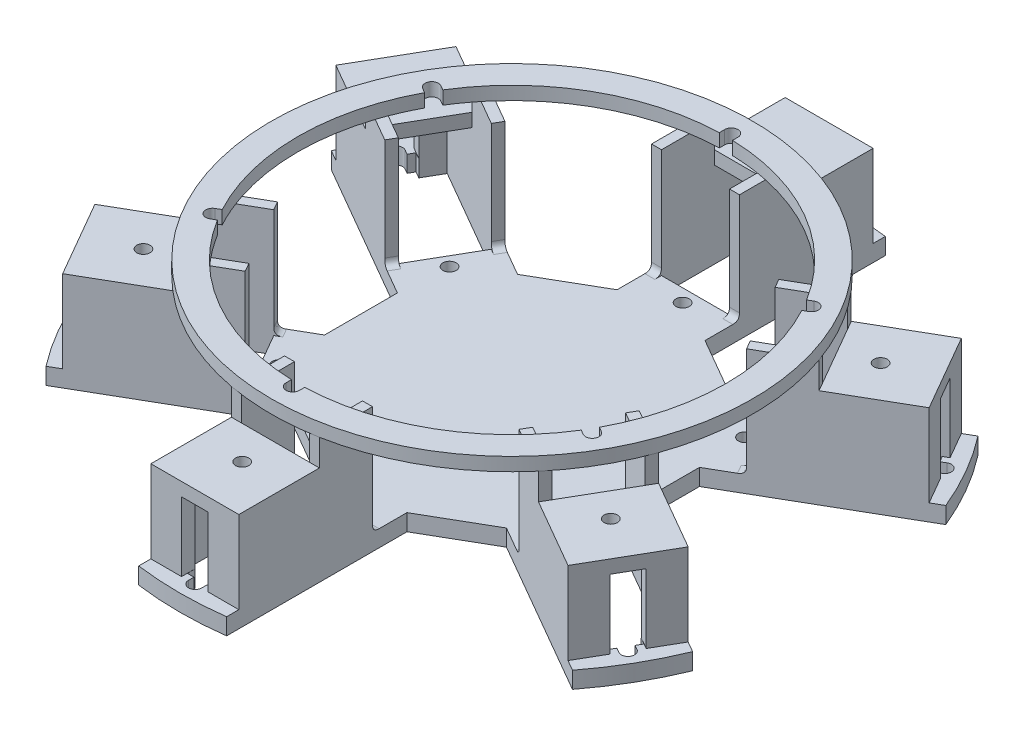
SolidWorks part; units mm, degrees
material "ABS"
ref_plane "Front" through (0, 0, 0) normal (0, 0, 1) x (1, 0, 0)
ref_plane "Top" through (0, 0, 0) normal (0, 1, 0) x (1, 0, 0)
ref_plane "Right" through (0, 0, 0) normal (1, 0, 0) x (0, 0, -1)
sketch "Sketch1" plane through (0, 0, 0) normal (0, 1, 0) x (1, 0, 0)
  line L0 (0, -63.5) -> (0, -61.8094) construction
  line L1 (0, 63.5) -> (-54.9926, 31.75) construction
  line L2 (-54.9926, 31.75) -> (-54.9926, -31.75) construction
  line L3 (-54.9926, -31.75) -> (0, -63.5) construction
  line L4 (0, -63.5) -> (54.9926, -31.75) construction
  line L5 (54.9926, -31.75) -> (54.9926, 31.75) construction
  line L6 (54.9926, 31.75) -> (0, 63.5) construction
  line L7 (47.0396, 34.6639) -> (27.121, 23.1639)
  line L8 (-6.5, 58.0694) -> (-2.5207, 58.0694)
  line L9 (-6.5, 58.0694) -> (-6.5, 35.0694)
  line L10 (-6.5, 35.0694) -> (6.5, 35.0694)
  line L11 (6.5, 58.0694) -> (6.5, 35.0694)
  line L12 (-6.5, 58.0694) -> (6.5, 35.0694) construction
  line L13 (-6.5, 35.0694) -> (6.5, 58.0694) construction
  line L14 (47.0396, 34.6639) -> (49.0292, 31.2177)
  line L15 (53.5396, 23.4055) -> (33.621, 11.9055)
  line L16 (27.121, 23.1639) -> (33.621, 11.9055)
  line L17 (53.5396, -23.4055) -> (33.621, -11.9055)
  line L18 (53.5396, -23.4055) -> (51.5499, -26.8517)
  line L19 (47.0396, -34.6639) -> (27.121, -23.1639)
  line L20 (33.621, -11.9055) -> (27.121, -23.1639)
  line L21 (6.5, -58.0694) -> (6.5, -35.0694)
  line L22 (6.5, -58.0694) -> (2.5207, -58.0694)
  line L23 (-6.5, -58.0694) -> (-6.5, -35.0694)
  line L24 (6.5, -35.0694) -> (-6.5, -35.0694)
  line L25 (-47.0396, -34.6639) -> (-27.121, -23.1639)
  line L26 (-47.0396, -34.6639) -> (-49.0292, -31.2177)
  line L27 (-53.5396, -23.4055) -> (-33.621, -11.9055)
  line L28 (-27.121, -23.1639) -> (-33.621, -11.9055)
  line L29 (-53.5396, 23.4055) -> (-33.621, 11.9055)
  line L30 (-53.5396, 23.4055) -> (-51.5499, 26.8517)
  line L31 (-47.0396, 34.6639) -> (-27.121, 23.1639)
  line L32 (-33.621, 11.9055) -> (-27.121, 23.1639)
  line L33 (-1.27, 60.5394) -> (-1.27, 59.5132)
  line L34 (-1.27, 59.5132) -> (-2.5207, 59.5132)
  line L35 (-2.5207, 59.5132) -> (-2.5207, 58.0694)
  line L37 (2.5207, 59.5132) -> (2.5207, 58.0694)
  line L38 (1.27, 59.5132) -> (2.5207, 59.5132)
  line L39 (1.27, 60.5394) -> (1.27, 59.5132)
  line L40 (0, 53.87) -> (0, 63.5) construction
  line L41 (51.7937, 31.3696) -> (50.9049, 30.8564)
  line L42 (50.9049, 30.8564) -> (50.2796, 31.9396)
  line L43 (50.2796, 31.9396) -> (49.0292, 31.2177)
  line L45 (52.8003, 27.5736) -> (51.5499, 26.8517)
  line L46 (52.1749, 28.6567) -> (52.8003, 27.5736)
  line L47 (53.0637, 29.1699) -> (52.1749, 28.6567)
  line L48 (53.0637, -29.1699) -> (52.1749, -28.6567)
  line L49 (52.1749, -28.6567) -> (52.8003, -27.5736)
  line L50 (52.8003, -27.5736) -> (51.5499, -26.8517)
  line L52 (50.2796, -31.9396) -> (49.0292, -31.2177)
  line L53 (50.9049, -30.8564) -> (50.2796, -31.9396)
  line L54 (51.7937, -31.3696) -> (50.9049, -30.8564)
  line L55 (1.27, -60.5394) -> (1.27, -59.5132)
  line L56 (1.27, -59.5132) -> (2.5207, -59.5132)
  line L57 (2.5207, -59.5132) -> (2.5207, -58.0694)
  line L59 (-2.5207, -59.5132) -> (-2.5207, -58.0694)
  line L60 (-1.27, -59.5132) -> (-2.5207, -59.5132)
  line L61 (-1.27, -60.5394) -> (-1.27, -59.5132)
  line L62 (-51.7937, -31.3696) -> (-50.9049, -30.8564)
  line L63 (-50.9049, -30.8564) -> (-50.2796, -31.9396)
  line L64 (-50.2796, -31.9396) -> (-49.0292, -31.2177)
  line L66 (-52.8003, -27.5736) -> (-51.5499, -26.8517)
  line L67 (-52.1749, -28.6567) -> (-52.8003, -27.5736)
  line L68 (-53.0637, -29.1699) -> (-52.1749, -28.6567)
  line L69 (-53.0637, 29.1699) -> (-52.1749, 28.6567)
  line L70 (-52.1749, 28.6567) -> (-52.8003, 27.5736)
  line L71 (-52.8003, 27.5736) -> (-51.5499, 26.8517)
  line L73 (-50.2796, 31.9396) -> (-49.0292, 31.2177)
  line L74 (-50.9049, 30.8564) -> (-50.2796, 31.9396)
  line L75 (-51.7937, 31.3696) -> (-50.9049, 30.8564)
  line L76 (2.5207, 58.0694) -> (6.5, 58.0694)
  line L77 (-49.0292, 31.2177) -> (-47.0396, 34.6639)
  line L78 (-51.5499, -26.8517) -> (-53.5396, -23.4055)
  line L79 (0, -58.0694) -> (0, 54.9926) construction
  line L80 (-2.5207, -58.0694) -> (-6.5, -58.0694)
  line L81 (49.0292, -31.2177) -> (47.0396, -34.6639)
  line L82 (51.5499, 26.8517) -> (53.5396, 23.4055)
  circle A0 centre (0, 0) radius 63.5
  circle A1 centre (0, 0) radius 54.9926 construction
  arc A2 (1.27, 60.5394) -> (-1.27, 60.5394) centre (0, 60.5394) ccw
  circle A3 centre (0, 32.5994) radius 1.27
  circle A5 centre (28.2319, 16.2997) radius 1.27
  circle A7 centre (28.2319, -16.2997) radius 1.27
  circle A9 centre (0, -32.5994) radius 1.27
  circle A11 centre (-28.2319, -16.2997) radius 1.27
  circle A13 centre (-28.2319, 16.2997) radius 1.27
  circle A14 centre (-52.4287, 30.2697) radius 1.27 [skipped]
  circle A15 centre (-52.4287, -30.2697) radius 1.27 [skipped]
  circle A16 centre (0, -60.5394) radius 1.27 [skipped]
  circle A17 centre (52.4287, -30.2697) radius 1.27 [skipped]
  circle A18 centre (52.4287, 30.2697) radius 1.27 [skipped]
  arc A19 (53.0637, 29.1699) -> (51.7937, 31.3696) centre (52.4287, 30.2697) ccw
  arc A20 (51.7937, -31.3696) -> (53.0637, -29.1699) centre (52.4287, -30.2697) ccw
  arc A21 (-1.27, -60.5394) -> (1.27, -60.5394) centre (0, -60.5394) ccw
  arc A22 (-53.0637, -29.1699) -> (-51.7937, -31.3696) centre (-52.4287, -30.2697) ccw
  arc A23 (-51.7937, 31.3696) -> (-53.0637, 29.1699) centre (-52.4287, 30.2697) ccw
  point P3 (0, 46.5694)
  point P11 (0, 0)
  point P13 (0, 0)
  point P14 (0, 0)
  point P64 (0, 0)
  point P69 (0, 52.67)
  point P120 (0, 0)
  point P121 (0, 0)
  point P122 (0, 46.5694)
  dimension "D1" = 127
  dimension "D4" = 2.54
  dimension "D5" = 2.54
  dimension "D2" = 23
  dimension "D3" = 13
  dimension "D6" = 27.94
  dimension "D7" = 13.97
  dimension "D9" = 6
  dimension "D10" = 1.4438
  dimension "D8" = 6
extrude "Boss-Extrude2" add sketch "Sketch1" along normal blind 3.175
sketch "Sketch2" plane through (0, 3.175, 0) normal (0, 1, 0) x (1, 0, 0)
  line L0 (0, 0) -> (-8.405, 62.9413) construction
  line L1 (0, 0) -> (-50.3063, 38.7496) construction
  line L2 (0, 0) -> (-25.4, 43.9941) construction
  line L3 (-50.3063, 38.7496) -> (-8.405, 62.9413) construction
  line L4 (-27.121, 23.1639) -> (-6.5, 35.0694) construction
  line L6 (-8.405, 28.4804) -> (-20.4623, 21.5192)
  line L7 (-20.4623, 21.5192) -> (-50.3063, 38.7496)
  line L8 (-27.121, 23.1639) -> (-47.0396, 34.6639) construction
  line L9 (-8.405, 28.4804) -> (-8.405, 62.9413)
  line L25 (-6.5, 58.0694) -> (-6.5, 35.0694) construction
  line L26 (8.405, 28.4804) -> (8.405, 62.9413)
  line L27 (20.4623, 21.5192) -> (8.405, 28.4804)
  line L28 (20.4623, 21.5192) -> (50.3063, 38.7496)
  line L29 (28.8673, 6.9613) -> (58.7113, 24.1917)
  line L30 (28.8673, -6.9613) -> (28.8673, 6.9613)
  line L31 (28.8673, -6.9613) -> (58.7113, -24.1917)
  line L32 (20.4623, -21.5192) -> (50.3063, -38.7496)
  line L33 (8.405, -28.4804) -> (20.4623, -21.5192)
  line L34 (8.405, -28.4804) -> (8.405, -62.9413)
  line L35 (-8.405, -28.4804) -> (-8.405, -62.9413)
  line L36 (-20.4623, -21.5192) -> (-8.405, -28.4804)
  line L37 (-20.4623, -21.5192) -> (-50.3063, -38.7496)
  line L38 (-28.8673, -6.9613) -> (-58.7113, -24.1917)
  line L39 (-28.8673, 6.9613) -> (-28.8673, -6.9613)
  line L40 (-28.8673, 6.9613) -> (-58.7113, 24.1917)
  circle A0 centre (0, 0) radius 63.5 construction
  arc A1 (-8.405, 62.9413) -> (-50.3063, 38.7496) centre (0, 0) ccw
  arc A7 (50.3063, 38.7496) -> (8.405, 62.9413) centre (0, 0) ccw
  arc A8 (58.7113, -24.1917) -> (58.7113, 24.1917) centre (0, 0) ccw
  arc A9 (8.405, -62.9413) -> (50.3063, -38.7496) centre (0, 0) ccw
  arc A10 (-50.3063, -38.7496) -> (-8.405, -62.9413) centre (0, 0) ccw
  arc A11 (-58.7113, 24.1917) -> (-58.7113, -24.1917) centre (0, 0) ccw
  point P38 (0, 0)
  point P41 (0, 0)
  dimension "D1" = 1.905
  dimension "D2" = 6
extrude "Cut-Extrude1" cut sketch "Sketch2" against normal up to next
sketch "Sketch3" plane through (0, 3.175, 0) normal (0, 1, 0) x (1, 0, 0)
  line L0 (-6.5, 35.0694) -> (6.5, 35.0694) construction
  line L5 (47.0396, 34.6639) -> (27.121, 23.1639)
  line L6 (27.121, 23.1639) -> (26.1685, 24.8137)
  line L8 (-6.5, 58.0694) -> (-6.5, 35.0694)
  line L9 (-6.5, 35.0694) -> (-8.405, 35.0694)
  line L10 (-8.405, 58.7044) -> (-8.405, 35.0694)
  line L11 (0, 60.5394) -> (0, 32.9218) construction
  line L12 (6.5, 35.0694) -> (8.405, 35.0694)
  line L13 (8.405, 58.7044) -> (8.405, 35.0694)
  line L15 (6.5, 58.0694) -> (6.5, 35.0694)
  line L57 (-8.405, 28.4804) -> (-8.405, 62.9413) construction
  line L58 (8.405, 62.9413) -> (8.405, 28.4804) construction
  line L59 (-6.5, 58.0694) -> (6.5, 58.0694)
  line L60 (-8.405, 58.7044) -> (-8.405, 60.6094)
  line L61 (-8.405, 60.6094) -> (8.405, 60.6094)
  line L62 (8.405, 58.7044) -> (8.405, 60.6094)
  line L63 (46.637, 36.6312) -> (26.1685, 24.8137)
  line L64 (33.621, 11.9055) -> (34.5735, 10.2558)
  line L65 (55.042, 22.0733) -> (34.5735, 10.2558)
  line L66 (53.5396, 23.4055) -> (33.621, 11.9055)
  line L67 (47.0396, 34.6639) -> (53.5396, 23.4055)
  line L68 (46.637, 36.6312) -> (48.2868, 37.5837)
  line L69 (48.2868, 37.5837) -> (56.6918, 23.0258)
  line L70 (55.042, 22.0733) -> (56.6918, 23.0258)
  line L71 (52.4287, 30.2697) -> (28.5111, 16.4609) construction
  line L72 (53.5396, -23.4055) -> (33.621, -11.9055)
  line L73 (33.621, -11.9055) -> (34.5735, -10.2558)
  line L74 (55.042, -22.0733) -> (34.5735, -10.2558)
  line L75 (27.121, -23.1639) -> (26.1685, -24.8137)
  line L76 (46.637, -36.6312) -> (26.1685, -24.8137)
  line L77 (47.0396, -34.6639) -> (27.121, -23.1639)
  line L78 (53.5396, -23.4055) -> (47.0396, -34.6639)
  line L79 (55.042, -22.0733) -> (56.6918, -23.0258)
  line L80 (56.6918, -23.0258) -> (48.2868, -37.5837)
  line L81 (46.637, -36.6312) -> (48.2868, -37.5837)
  line L82 (52.4287, -30.2697) -> (28.5111, -16.4609) construction
  line L83 (6.5, -58.0694) -> (6.5, -35.0694)
  line L84 (6.5, -35.0694) -> (8.405, -35.0694)
  line L85 (8.405, -58.7044) -> (8.405, -35.0694)
  line L86 (-6.5, -35.0694) -> (-8.405, -35.0694)
  line L87 (-8.405, -58.7044) -> (-8.405, -35.0694)
  line L88 (-6.5, -58.0694) -> (-6.5, -35.0694)
  line L89 (6.5, -58.0694) -> (-6.5, -58.0694)
  line L90 (8.405, -58.7044) -> (8.405, -60.6094)
  line L91 (8.405, -60.6094) -> (-8.405, -60.6094)
  line L92 (-8.405, -58.7044) -> (-8.405, -60.6094)
  line L93 (0, -60.5394) -> (0, -32.9218) construction
  line L94 (-47.0396, -34.6639) -> (-27.121, -23.1639)
  line L95 (-27.121, -23.1639) -> (-26.1685, -24.8137)
  line L96 (-46.637, -36.6312) -> (-26.1685, -24.8137)
  line L97 (-33.621, -11.9055) -> (-34.5735, -10.2558)
  line L98 (-55.042, -22.0733) -> (-34.5735, -10.2558)
  line L99 (-53.5396, -23.4055) -> (-33.621, -11.9055)
  line L100 (-47.0396, -34.6639) -> (-53.5396, -23.4055)
  line L101 (-46.637, -36.6312) -> (-48.2868, -37.5837)
  line L102 (-48.2868, -37.5837) -> (-56.6918, -23.0258)
  line L103 (-55.042, -22.0733) -> (-56.6918, -23.0258)
  line L104 (-52.4287, -30.2697) -> (-28.5111, -16.4609) construction
  line L105 (-53.5396, 23.4055) -> (-33.621, 11.9055)
  line L106 (-33.621, 11.9055) -> (-34.5735, 10.2558)
  line L107 (-55.042, 22.0733) -> (-34.5735, 10.2558)
  line L108 (-27.121, 23.1639) -> (-26.1685, 24.8137)
  line L109 (-46.637, 36.6312) -> (-26.1685, 24.8137)
  line L110 (-47.0396, 34.6639) -> (-27.121, 23.1639)
  line L111 (-53.5396, 23.4055) -> (-47.0396, 34.6639)
  line L112 (-55.042, 22.0733) -> (-56.6918, 23.0258)
  line L113 (-56.6918, 23.0258) -> (-48.2868, 37.5837)
  line L114 (-46.637, 36.6312) -> (-48.2868, 37.5837)
  line L115 (-52.4287, 30.2697) -> (-28.5111, 16.4609) construction
  point P0 (0, 0)
  point P1 (0, 0)
  point P64 (0, 0)
  point P85 (0, 0)
  dimension "D1" = 6
  dimension "D2" = 1.905
  dimension "D3" = 2.54
extrude "Boss-Extrude3" add sketch "Sketch3" along normal blind 13.208
sketch "Sketch4" plane through (0, 0, -60.6094) normal (0, 0, -1) x (-1, 0, 0)
  line L0 (0, 3.175) -> (0, 16.383) construction
  line L1 (8.405, 3.175) -> (-8.405, 3.175) construction
  line L2 (-8.405, 16.383) -> (8.405, 16.383) construction
  line L4 (-2.54, 16.383) -> (2.54, 16.383)
  line L5 (-2.54, 16.383) -> (-2.54, 3.175)
  line L6 (-2.54, 3.175) -> (2.54, 3.175)
  line L7 (2.54, 16.383) -> (2.54, 3.175)
  line L8 (-2.54, 16.383) -> (2.54, 3.175) construction
  line L9 (-2.54, 3.175) -> (2.54, 16.383) construction
  point P6 (0, 9.779)
  dimension "D1" = 5.08
extrude "Cut-Extrude2" cut sketch "Sketch4" against normal blind 13.208
ref_point "Point1"
pattern_circular "CirPattern2" count 6 every 60 about axis through (0, 3.175, 0) along (0, 1, 0) of "Cut-Extrude2"
fillet "Fillet1" radius 1.27 12 edges at (26.6448, 3.175, -23.9888) (34.0973, 3.175, -11.0807) (34.0973, 3.175, 11.0807) (26.6448, 3.175, 23.9888) (7.4525, 3.175, 35.0694) (-7.4525, 3.175, 35.0694) (-26.6448, 3.175, 23.9888) (-34.0973, 3.175, 11.0807) (-34.0973, 3.175, -11.0807) (-26.6448, 3.175, -23.9888) (-7.4525, 3.175, -35.0694) (7.4525, 3.175, -35.0694) conic rho 0.5
sketch "Sketch5" plane through (0, 16.383, 0) normal (0, 1, 0) x (1, 0, 0)
  line L0 (0, 52.67) -> (0, 35.0694) construction
  line L2 (-6.5, 35.0694) -> (6.5, 35.0694) construction
  line L10 (-6.5, 35.0694) -> (-6.5, 58.0694) construction
  line L11 (-6.5, 46.5694) -> (-8.405, 46.5694)
  line L12 (-6.5, 46.5694) -> (-6.5, 35.0694)
  line L13 (-6.5, 35.0694) -> (-8.405, 35.0694)
  line L14 (-8.405, 46.5694) -> (-8.405, 35.0694)
  line L15 (-8.405, 35.0694) -> (-6.5, 35.0694) construction
  line L16 (-8.405, 60.6094) -> (-8.405, 35.0694) construction
  line L17 (6.5, 35.0694) -> (8.405, 35.0694)
  line L18 (8.405, 46.5694) -> (8.405, 35.0694)
  line L19 (6.5, 46.5694) -> (8.405, 46.5694)
  line L20 (6.5, 46.5694) -> (6.5, 35.0694)
  line L21 (35.3322, 31.9164) -> (25.3729, 26.1664)
  line L22 (35.3322, 31.9164) -> (34.3797, 33.5661)
  line L23 (34.3797, 33.5661) -> (24.4204, 27.8161)
  line L24 (25.3729, 26.1664) -> (24.4204, 27.8161)
  line L25 (31.8729, 14.908) -> (32.8254, 13.2582)
  line L26 (42.7847, 19.0082) -> (32.8254, 13.2582)
  line L27 (41.8322, 20.658) -> (42.7847, 19.0082)
  line L28 (41.8322, 20.658) -> (31.8729, 14.908)
  line L29 (43.5584, -11.638) -> (33.5992, -5.888)
  line L30 (43.5584, -11.638) -> (44.5109, -9.9882)
  line L31 (44.5109, -9.9882) -> (34.5517, -4.2382)
  line L32 (33.5992, -5.888) -> (34.5517, -4.2382)
  line L33 (27.0992, -17.1463) -> (26.1467, -18.7961)
  line L34 (36.1059, -24.5461) -> (26.1467, -18.7961)
  line L35 (37.0584, -22.8963) -> (36.1059, -24.5461)
  line L36 (37.0584, -22.8963) -> (27.0992, -17.1463)
  line L37 (9.9524, -40.5392) -> (9.9524, -29.0392)
  line L38 (9.9524, -40.5392) -> (11.8574, -40.5392)
  line L39 (11.8574, -40.5392) -> (11.8574, -29.0392)
  line L40 (9.9524, -29.0392) -> (11.8574, -29.0392)
  line L41 (-3.0476, -29.0392) -> (-4.9526, -29.0392)
  line L42 (-4.9526, -40.5392) -> (-4.9526, -29.0392)
  line L43 (-3.0476, -40.5392) -> (-4.9526, -40.5392)
  line L44 (-3.0476, -40.5392) -> (-3.0476, -29.0392)
  line L45 (-31.8798, -25.8862) -> (-21.9205, -20.1362)
  line L46 (-31.8798, -25.8862) -> (-30.9273, -27.5359)
  line L47 (-30.9273, -27.5359) -> (-20.968, -21.7859)
  line L48 (-21.9205, -20.1362) -> (-20.968, -21.7859)
  line L49 (-28.4205, -8.8778) -> (-29.373, -7.228)
  line L50 (-39.3323, -12.978) -> (-29.373, -7.228)
  line L51 (-38.3798, -14.6278) -> (-39.3323, -12.978)
  line L52 (-38.3798, -14.6278) -> (-28.4205, -8.8778)
  line L53 (-40.106, 17.6682) -> (-30.1467, 11.9182)
  line L54 (-40.106, 17.6682) -> (-41.0585, 16.0184)
  line L55 (-41.0585, 16.0184) -> (-31.0992, 10.2684)
  line L56 (-30.1467, 11.9182) -> (-31.0992, 10.2684)
  line L57 (-23.6467, 23.1765) -> (-22.6942, 24.8263)
  line L58 (-32.6535, 30.5763) -> (-22.6942, 24.8263)
  line L59 (-33.606, 28.9265) -> (-32.6535, 30.5763)
  line L60 (-33.606, 28.9265) -> (-23.6467, 23.1765)
  point P62 (1.7262, 3.0151)
  dimension "D1" = 6
sketch "Sketch8" plane through (0, 0, 0) normal (0, -1, 0) x (1, 0, 0)
  line L0 (-8.405, 28.4804) -> (-8.405, 62.9413) construction
  line L1 (-6.5, 35.0694) -> (-8.405, 35.0694)
  line L2 (-6.5, 35.0694) -> (-6.5, 58.0694)
  line L3 (-6.5, 58.0694) -> (-8.405, 58.0694)
  line L4 (-8.405, 35.0694) -> (-8.405, 58.0694)
  line L5 (0, 55.14) -> (0, 32.5994) construction
  line L6 (-6.5, 58.0694) -> (-2.5207, 58.0694) construction
  line L7 (6.5, 58.0694) -> (8.405, 58.0694)
  line L8 (8.405, 35.0694) -> (8.405, 58.0694)
  line L9 (6.5, 35.0694) -> (8.405, 35.0694)
  line L10 (6.5, 35.0694) -> (6.5, 58.0694)
  line L12 (48.8635, 20.7058) -> (49.816, 19.056)
  line L13 (29.8975, 7.556) -> (49.816, 19.056)
  line L14 (28.945, 9.2058) -> (29.8975, 7.556)
  line L15 (28.945, 9.2058) -> (48.8635, 20.7058)
  line L16 (22.445, 20.4642) -> (42.3635, 31.9642)
  line L17 (22.445, 20.4642) -> (21.4925, 22.1139)
  line L18 (21.4925, 22.1139) -> (41.411, 33.6139)
  line L19 (42.3635, 31.9642) -> (41.411, 33.6139)
  line L20 (37.6875, -34.6639) -> (36.735, -36.3137)
  line L21 (16.8164, -24.8137) -> (36.735, -36.3137)
  line L22 (17.7689, -23.1639) -> (16.8164, -24.8137)
  line L23 (17.7689, -23.1639) -> (37.6875, -34.6639)
  line L24 (24.2689, -11.9055) -> (44.1875, -23.4055)
  line L25 (24.2689, -11.9055) -> (25.2214, -10.2558)
  line L26 (25.2214, -10.2558) -> (45.14, -21.7558)
  line L27 (44.1875, -23.4055) -> (45.14, -21.7558)
  line L28 (-15.8521, -52.67) -> (-17.7571, -52.67)
  line L29 (-17.7571, -29.67) -> (-17.7571, -52.67)
  line L30 (-15.8521, -29.67) -> (-17.7571, -29.67)
  line L31 (-15.8521, -29.67) -> (-15.8521, -52.67)
  line L32 (-2.8521, -29.67) -> (-2.8521, -52.67)
  line L33 (-2.8521, -29.67) -> (-0.9471, -29.67)
  line L34 (-0.9471, -29.67) -> (-0.9471, -52.67)
  line L35 (-2.8521, -52.67) -> (-0.9471, -52.67)
  line L36 (-58.2156, -15.3064) -> (-59.1681, -13.6566)
  line L37 (-39.2495, -2.1566) -> (-59.1681, -13.6566)
  line L38 (-38.297, -3.8064) -> (-39.2495, -2.1566)
  line L39 (-38.297, -3.8064) -> (-58.2156, -15.3064)
  line L40 (-31.797, -15.0647) -> (-51.7156, -26.5647)
  line L41 (-31.797, -15.0647) -> (-30.8445, -16.7145)
  line L42 (-30.8445, -16.7145) -> (-50.7631, -28.2145)
  line L43 (-51.7156, -26.5647) -> (-50.7631, -28.2145)
  line L44 (-47.0396, 40.0633) -> (-46.0871, 41.7131)
  line L45 (-26.1685, 30.2131) -> (-46.0871, 41.7131)
  line L46 (-27.121, 28.5633) -> (-26.1685, 30.2131)
  line L47 (-27.121, 28.5633) -> (-47.0396, 40.0633)
  line L48 (-33.621, 17.305) -> (-53.5396, 28.805)
  line L49 (-33.621, 17.305) -> (-34.5735, 15.6552)
  line L50 (-34.5735, 15.6552) -> (-54.4921, 27.1552)
  line L51 (-53.5396, 28.805) -> (-54.4921, 27.1552)
  point P59 (-4.676, 2.6997)
  dimension "D1" = 6
extrude "Boss-Extrude6" [suppressed] add sketch "Sketch8" along normal blind 6.35
sketch "Sketch9" plane through (0, 0, 0) normal (0, -1, 0) x (1, 0, 0)
  line L0 (8.405, -28.4804) -> (-8.405, -28.4804)
  line L1 (-8.405, 24.9687) -> (8.405, 24.9687)
  line L2 (8.405, 24.9687) -> (8.405, 35.0925)
  line L3 (8.405, 62.9413) -> (8.405, 28.4804) construction
  line L4 (8.405, 35.0925) -> (44.2076, 42.1004)
  line L5 (44.2076, 42.1004) -> (56.6527, 22.889)
  line L6 (56.6527, 22.889) -> (57.2815, -47.068)
  line L7 (57.2815, -47.068) -> (-16.4259, -92.7274)
  line L8 (-16.4259, -92.7274) -> (-91.3916, -39.5846)
  line L9 (-91.3916, -39.5846) -> (-78.4595, 36.5934)
  line L10 (-78.4595, 36.5934) -> (-30.3683, 56.5286)
  line L11 (-30.3683, 56.5286) -> (-8.405, 35.0925)
  line L12 (-8.405, 28.4804) -> (-8.405, 62.9413) construction
  line L13 (-8.405, 35.0925) -> (-8.405, 24.9687)
extrude "Cut-Extrude5" [suppressed] cut sketch "Sketch9" against normal through all
sketch "Sketch11" plane through (0, 16.383, 0) normal (0, 1, 0) x (1, 0, 0)
  line L0 (48.2868, 37.5837) -> (34.9477, 29.8823)
  line L1 (-8.405, 60.6094) -> (8.405, 60.6094)
  line L2 (-8.405, 60.6094) -> (-8.405, 45.2068)
  line L3 (-8.405, 45.2068) -> (8.405, 45.2068)
  line L4 (8.405, 60.6094) -> (8.405, 45.2068)
  line L5 (48.2868, 37.5837) -> (56.6918, 23.0258)
  line L6 (56.6918, 23.0258) -> (43.3527, 15.3244)
  line L7 (34.9477, 29.8823) -> (43.3527, 15.3244)
  line L8 (56.6918, -23.0258) -> (43.3527, -15.3244)
  line L9 (56.6918, -23.0258) -> (48.2868, -37.5837)
  line L10 (48.2868, -37.5837) -> (34.9477, -29.8823)
  line L11 (43.3527, -15.3244) -> (34.9477, -29.8823)
  line L12 (8.405, -60.6094) -> (8.405, -45.2068)
  line L13 (8.405, -60.6094) -> (-8.405, -60.6094)
  line L14 (-8.405, -60.6094) -> (-8.405, -45.2068)
  line L15 (8.405, -45.2068) -> (-8.405, -45.2068)
  line L16 (-48.2868, -37.5837) -> (-34.9477, -29.8823)
  line L17 (-48.2868, -37.5837) -> (-56.6918, -23.0258)
  line L18 (-56.6918, -23.0258) -> (-43.3527, -15.3244)
  line L19 (-34.9477, -29.8823) -> (-43.3527, -15.3244)
  line L20 (-56.6918, 23.0258) -> (-43.3527, 15.3244)
  line L21 (-56.6918, 23.0258) -> (-48.2868, 37.5837)
  line L22 (-48.2868, 37.5837) -> (-34.9477, 29.8823)
  line L23 (-43.3527, 15.3244) -> (-34.9477, 29.8823)
  line L24 (8.405, 46.5694) -> (8.405, 35.0694) construction
  point P4 (0, 0)
  point P28 (0, 0)
  point P30 (0, 0)
  dimension "D1" = 6
extrude "Boss-Extrude7" add sketch "Sketch11" along normal blind 2.54
sketch "Sketch12" plane through (0, 16.383, 0) normal (0, 1, 0) x (1, 0, 0)
  line L0 (34.9477, 29.8823) -> (35.9002, 28.2325)
  line L1 (-8.405, 45.2068) -> (-6.5, 45.2068)
  line L2 (-8.405, 45.2068) -> (-8.405, 35.0694)
  line L3 (-8.405, 35.0694) -> (-6.5, 35.0694)
  line L4 (-6.5, 45.2068) -> (-6.5, 35.0694)
  line L5 (0, 45.2068) -> (0, 35.0694) construction
  line L6 (-8.405, 45.2068) -> (8.405, 45.2068) construction
  line L7 (8.405, 35.0694) -> (6.5, 35.0694)
  line L8 (6.5, 45.2068) -> (6.5, 35.0694)
  line L9 (8.405, 45.2068) -> (6.5, 45.2068)
  line L10 (8.405, 45.2068) -> (8.405, 35.0694)
  line L11 (34.9477, 29.8823) -> (26.1685, 24.8137)
  line L12 (26.1685, 24.8137) -> (27.121, 23.1639)
  line L13 (35.9002, 28.2325) -> (27.121, 23.1639)
  line L14 (34.5735, 10.2558) -> (33.621, 11.9055)
  line L15 (42.4002, 16.9742) -> (33.621, 11.9055)
  line L16 (43.3527, 15.3244) -> (42.4002, 16.9742)
  line L17 (43.3527, 15.3244) -> (34.5735, 10.2558)
  line L18 (39.1502, 22.6034) -> (30.371, 17.5347) construction
  line L19 (43.3527, -15.3244) -> (42.4002, -16.9742)
  line L20 (43.3527, -15.3244) -> (34.5735, -10.2558)
  line L21 (34.5735, -10.2558) -> (33.621, -11.9055)
  line L22 (42.4002, -16.9742) -> (33.621, -11.9055)
  line L23 (26.1685, -24.8137) -> (27.121, -23.1639)
  line L24 (35.9002, -28.2325) -> (27.121, -23.1639)
  line L25 (34.9477, -29.8823) -> (35.9002, -28.2325)
  line L26 (34.9477, -29.8823) -> (26.1685, -24.8137)
  line L27 (39.1502, -22.6034) -> (30.371, -17.5347) construction
  line L28 (8.405, -45.2068) -> (6.5, -45.2068)
  line L29 (8.405, -45.2068) -> (8.405, -35.0694)
  line L30 (8.405, -35.0694) -> (6.5, -35.0694)
  line L31 (6.5, -45.2068) -> (6.5, -35.0694)
  line L32 (-8.405, -35.0694) -> (-6.5, -35.0694)
  line L33 (-6.5, -45.2068) -> (-6.5, -35.0694)
  line L34 (-8.405, -45.2068) -> (-6.5, -45.2068)
  line L35 (-8.405, -45.2068) -> (-8.405, -35.0694)
  line L36 (0, -45.2068) -> (0, -35.0694) construction
  line L37 (-34.9477, -29.8823) -> (-35.9002, -28.2325)
  line L38 (-34.9477, -29.8823) -> (-26.1685, -24.8137)
  line L39 (-26.1685, -24.8137) -> (-27.121, -23.1639)
  line L40 (-35.9002, -28.2325) -> (-27.121, -23.1639)
  line L41 (-34.5735, -10.2558) -> (-33.621, -11.9055)
  line L42 (-42.4002, -16.9742) -> (-33.621, -11.9055)
  line L43 (-43.3527, -15.3244) -> (-42.4002, -16.9742)
  line L44 (-43.3527, -15.3244) -> (-34.5735, -10.2558)
  line L45 (-39.1502, -22.6034) -> (-30.371, -17.5347) construction
  line L46 (-43.3527, 15.3244) -> (-42.4002, 16.9742)
  line L47 (-43.3527, 15.3244) -> (-34.5735, 10.2558)
  line L48 (-34.5735, 10.2558) -> (-33.621, 11.9055)
  line L49 (-42.4002, 16.9742) -> (-33.621, 11.9055)
  line L50 (-26.1685, 24.8137) -> (-27.121, 23.1639)
  line L51 (-35.9002, 28.2325) -> (-27.121, 23.1639)
  line L52 (-34.9477, 29.8823) -> (-35.9002, 28.2325)
  line L53 (-34.9477, 29.8823) -> (-26.1685, 24.8137)
  line L54 (-39.1502, 22.6034) -> (-30.371, 17.5347) construction
  point P15 (0, 0)
  point P67 (0, 0)
  dimension "D1" = 6
extrude "Boss-Extrude9" add sketch "Sketch12" along normal blind 7.62
sketch "Sketch13" plane through (0, 24.003, 0) normal (0, 1, 0) x (1, 0, 0)
  line L0 (34.9477, 29.8823) -> (26.1685, 24.8137)
  line L1 (-8.405, 45.2068) -> (8.405, 45.2068)
  line L2 (-8.405, 45.2068) -> (-8.405, 35.0694)
  line L3 (-8.405, 35.0694) -> (8.405, 35.0694)
  line L4 (8.405, 45.2068) -> (8.405, 35.0694)
  line L5 (34.9477, 29.8823) -> (43.3527, 15.3244)
  line L6 (43.3527, 15.3244) -> (34.5735, 10.2558)
  line L7 (26.1685, 24.8137) -> (34.5735, 10.2558)
  line L8 (43.3527, -15.3244) -> (34.5735, -10.2558)
  line L9 (43.3527, -15.3244) -> (34.9477, -29.8823)
  line L10 (34.9477, -29.8823) -> (26.1685, -24.8137)
  line L11 (34.5735, -10.2558) -> (26.1685, -24.8137)
  line L12 (8.405, -45.2068) -> (8.405, -35.0694)
  line L13 (8.405, -45.2068) -> (-8.405, -45.2068)
  line L14 (-8.405, -45.2068) -> (-8.405, -35.0694)
  line L15 (8.405, -35.0694) -> (-8.405, -35.0694)
  line L16 (-34.9477, -29.8823) -> (-26.1685, -24.8137)
  line L17 (-34.9477, -29.8823) -> (-43.3527, -15.3244)
  line L18 (-43.3527, -15.3244) -> (-34.5735, -10.2558)
  line L19 (-26.1685, -24.8137) -> (-34.5735, -10.2558)
  line L20 (-43.3527, 15.3244) -> (-34.5735, 10.2558)
  line L21 (-43.3527, 15.3244) -> (-34.9477, 29.8823)
  line L22 (-34.9477, 29.8823) -> (-26.1685, 24.8137)
  line L23 (-34.5735, 10.2558) -> (-26.1685, 24.8137)
  point P28 (0, 0)
  point P32 (0, 0)
  point P33 (0, 0)
  point P34 (0, 0)
  dimension "D1" = 6
sketch "Sketch15" plane through (0, 24.003, 0) normal (0, 1, 0) x (1, 0, 0)
  circle A0 centre (0, 0) radius 45.9815
  circle A1 centre (0, 0) radius 40.9015
  dimension "D1" = 5.08
extrude "Boss-Extrude12" add sketch "Sketch15" along normal blind 2.54
sketch "Sketch16" plane through (0, 26.543, 0) normal (0, 1, 0) x (1, 0, 0)
  line L0 (0, 52.67) -> (0, 35.0694) construction
  line L1 (-1.27, 41.91) -> (-1.27, 39.1914)
  line L2 (-1.27, 39.1914) -> (1.27, 39.1914)
  line L3 (1.27, 39.1914) -> (1.27, 41.91)
  line L4 (35.6601, 22.0549) -> (33.3058, 20.6956)
  line L5 (33.3058, 20.6956) -> (34.5758, 18.4959)
  line L6 (34.5758, 18.4959) -> (36.9301, 19.8551)
  line L7 (36.9301, -19.8551) -> (34.5758, -18.4959)
  line L8 (34.5758, -18.4959) -> (33.3058, -20.6956)
  line L9 (33.3058, -20.6956) -> (35.6601, -22.0549)
  line L10 (1.27, -41.91) -> (1.27, -39.1914)
  line L11 (1.27, -39.1914) -> (-1.27, -39.1914)
  line L12 (-1.27, -39.1914) -> (-1.27, -41.91)
  line L13 (-35.6601, -22.0549) -> (-33.3058, -20.6956)
  line L14 (-33.3058, -20.6956) -> (-34.5758, -18.4959)
  line L15 (-34.5758, -18.4959) -> (-36.9301, -19.8551)
  line L16 (-36.9301, 19.8551) -> (-34.5758, 18.4959)
  line L17 (-34.5758, 18.4959) -> (-33.3058, 20.6956)
  line L18 (-33.3058, 20.6956) -> (-35.6601, 22.0549)
  arc A0 (1.27, 41.91) -> (-1.27, 41.91) centre (0, 41.91) ccw
  arc A2 (36.9301, 19.8551) -> (35.6601, 22.0549) centre (36.2951, 20.955) ccw
  arc A3 (35.6601, -22.0549) -> (36.9301, -19.8551) centre (36.2951, -20.955) ccw
  arc A4 (-1.27, -41.91) -> (1.27, -41.91) centre (0, -41.91) ccw
  arc A5 (-36.9301, -19.8551) -> (-35.6601, -22.0549) centre (-36.2951, -20.955) ccw
  arc A6 (-35.6601, 22.0549) -> (-36.9301, 19.8551) centre (-36.2951, 20.955) ccw
  point P35 (0, 0)
  dimension "D1" = 2.54
  dimension "D2" = 41.91
  dimension "D3" = 6
extrude "Cut-Extrude6" cut sketch "Sketch16" against normal blind 2.54
fillet "Fillet2" [suppressed] radius 5.08
sketch "Sketch17" plane through (0, 18.923, 0) normal (0, 1, 0) x (1, 0, 0)
  line L3 (-6.5, 51.567) -> (6.5, 51.567) construction
  line L4 (6.5, 35.0694) -> (6.5, 58.0694) construction
  line L5 (0, 52.67) -> (0, 35.0694) construction
  line L6 (-6.5, 58.0694) -> (-2.54, 58.0694) construction
  circle A0 centre (0, 51.567) radius 1.27
  circle A1 centre (44.6583, 25.7835) radius 1.27
  circle A2 centre (44.6583, -25.7835) radius 1.27
  circle A3 centre (0, -51.567) radius 1.27
  circle A4 centre (-44.6583, -25.7835) radius 1.27
  circle A5 centre (-44.6583, 25.7835) radius 1.27
  point P0 (0, 52.67)
  point P15 (45.6135, 26.335)
  point P18 (45.6135, -26.335)
  point P21 (0, -52.67)
  point P24 (-45.6135, -26.335)
  point P27 (-45.6135, 26.335)
  point P30 (0, 0)
  dimension "D2" = 2.54
  dimension "D1" = 6.5024
  dimension "D3" = 6
extrude "Cut-Extrude7" cut sketch "Sketch17" against normal through all both and the other way through all
